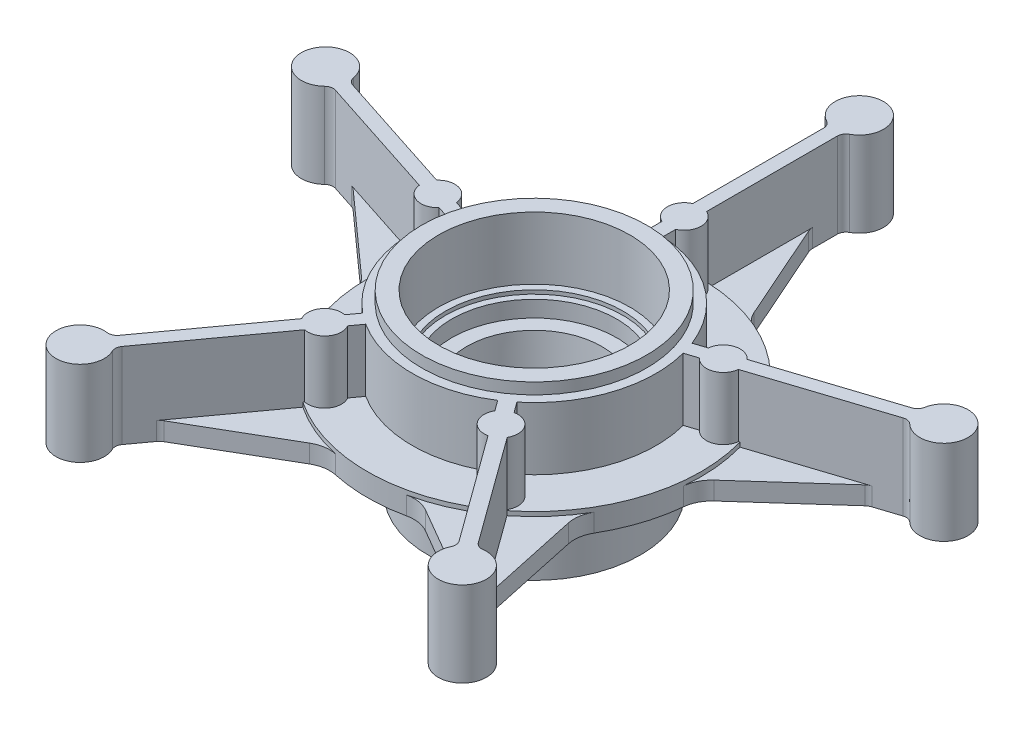
SolidWorks part; units mm, degrees
material "1060 Alloy"
ref_plane "Front Plane" through (0, 0, 0) normal (0, 0, 1) x (1, 0, 0)
ref_plane "Top Plane" through (0, 0, 0) normal (0, 1, 0) x (1, 0, 0)
ref_plane "Right Plane" through (0, 0, 0) normal (1, 0, 0) x (0, 0, -1)
sketch "Sketch1" plane through (0, 0, 0) normal (0, 0, 1) x (1, 0, 0)
  line L1 (89.8423, 2.6099) -> (97.5, 61)
  line L2 (97.5, 61) -> (133.5, 61)
  line L3 (133.5, 61) -> (133.5, 82)
  line L4 (133.5, 82) -> (97.5, 82)
  line L5 (97.5, 82) -> (97.5, 147)
  line L8 (0, 165) -> (0, 0)
  line L15 (71, 147) -> (71, 88)
  line L16 (71, 88) -> (66, 88)
  line L17 (66, 88) -> (66, 75)
  line L18 (66, 75) -> (54, 75)
  line L19 (54, 75) -> (51.5053, 40.9816)
  line L26 (48.5, 0) -> (86.8678, 0)
  line L27 (97.5, 147) -> (71, 147)
  line L28 (48.5, 0) -> (50.8833, 40.5398)
  line L29 (50.8833, 40.5398) -> (51.5053, 40.9816)
  arc A0 (86.8678, 0) -> (89.8423, 2.6099) centre (86.8678, 3) ccw
  point P19 (86, 0)
  point P22 (-86, 0)
  dimension "D10" = 3
  dimension "D2" = 48.5
  dimension "D3" = 133.5
  dimension "D4" = 71
  dimension "D5" = 36
  dimension "D6" = 21
  dimension "D7" = 54
  dimension "D13" = 5
  dimension "D14" = 13
revolve "Revolve1" add sketch "Sketch1" angle 360 about L8
sketch "Sketch2" plane through (0, 82, 0) normal (0, 1, 0) x (1, 0, 0)
  line L0 (-40.8786, 135.0059) -> (-6.3545, 213.0679)
  line L1 (5.5, 236.8593) -> (5.5, 217.1126)
  line L2 (-5.5, 236.8593) -> (-5.5, 217.1126)
  line L3 (0, 260) -> (0, 296.018)
  line L7 (40.8786, 135.0059) -> (6.3545, 213.0679)
  arc A0 (9.1731, 243.0182) -> (-9.1731, 243.0182) centre (0, 260) ccw
  circle A3 centre (0, 0) radius 133.5 construction
  arc A4 (53.6884, 122.2285) -> (-53.6884, 122.2285) centre (0, 0) ccw
  arc A5 (-40.8786, 135.0059) -> (-53.6884, 122.2285) centre (-63.7424, 145.1178) cw
  arc A6 (53.6884, 122.2285) -> (40.8786, 135.0059) centre (63.7424, 145.1178) cw
  arc A7 (6.3545, 213.0679) -> (5.5, 217.1126) centre (15.5, 217.1126) cw
  arc A8 (-6.3545, 213.0679) -> (-5.5, 217.1126) centre (-15.5, 217.1126) ccw
  arc A9 (5.5, 236.8593) -> (9.1731, 243.0182) centre (12.5, 236.8593) cw
  arc A10 (-5.5, 236.8593) -> (-9.1731, 243.0182) centre (-12.5, 236.8593) ccw
  point P15 (-45, 125.6871)
  point P20 (45, 125.6871)
  point P21 (5.5, 215)
  point P24 (-5.5, 215)
  dimension "D1" = 260
  dimension "D2" = 25
  dimension "D3" = 10
  dimension "D4" = 7
  dimension "D5" = 19.301
extrude "Boss-Extrude1" add sketch "Sketch2" against normal blind 21
pattern_circular "CirPattern1" count 5 every 72 about axis through (0, 0, 0) along (0, 1, 0) of "Boss-Extrude1"
sketch "Sketch3" plane through (0, 82, 0) normal (0, 1, 0) x (1, 0, 0)
  circle A0 centre (0, 0) radius 133.5
  circle A1 centre (0, 0) radius 294.6742
extrude "Cut-Extrude1" cut sketch "Sketch3" against normal blind 3.5
sketch "Sketch4" plane through (0, 78.5, 0) normal (0, 1, 0) x (1, 0, 0)
  line L0 (-5.5, 236.8593) -> (-5.5, 132.3288)
  line L1 (5.5, 236.8593) -> (5.5, 132.3288)
  line L2 (5.5, 107.6712) -> (5.5, 97.3447)
  line L3 (-5.5, 107.6712) -> (-5.5, 97.3447)
  arc A0 (9.1731, 243.0182) -> (-9.1731, 243.0182) centre (0, 260) ccw
  arc A1 (9.1731, 243.0182) -> (5.5, 236.8593) centre (12.5, 236.8593) ccw
  arc A2 (-5.5, 236.8593) -> (-9.1731, 243.0182) centre (-12.5, 236.8593) ccw
  arc A3 (5.5, 97.3447) -> (-5.5, 97.3447) centre (0, 0) ccw
  arc A4 (5.5, 107.6712) -> (5.5, 132.3288) centre (0, 120) ccw
  arc A5 (-5.5, 132.3288) -> (-5.5, 107.6712) centre (0, 120) ccw
  dimension "D1" = 27
  dimension "D2" = 140
extrude "Boss-Extrude2" add sketch "Sketch4" along normal blind 68
pattern_circular "CirPattern2" count 5 every 72 about axis through (0, 0, 0) along (0, 1, 0) of "Boss-Extrude2"
sketch "Sketch6" plane through (0, 147, 0) normal (0, 1, 0) x (1, 0, 0)
  circle A0 centre (0, 0) radius 312.0658
extrude "Cut-Extrude3" cut sketch "Sketch6" against normal blind 15
sketch "Sketch7" plane through (0, 132, 0) normal (0, 1, 0) x (1, 0, 0)
  circle A0 centre (0, 0) radius 90
  circle A1 centre (0, 0) radius 71
  dimension "D1" = 180
extrude "Boss-Extrude3" add sketch "Sketch7" along normal blind 9
sketch "Sketch8" plane through (0, 141, 0) normal (0, 1, 0) x (1, 0, 0)
  circle A0 centre (0, 0) radius 76.5
  dimension "D1" = 153
extrude "Cut-Extrude4" cut sketch "Sketch8" against normal blind 50
sketch "Sketch9" plane through (0, 61, 0) normal (0, -1, 0) x (1, 0, 0)
  circle A0 centre (0, 0) radius 94
  circle A1 centre (0, 0) radius 313.8454
extrude "Cut-Extrude5" cut sketch "Sketch9" against normal blind 3
sketch "Sketch10" plane through (0, 0, 0) normal (0, -1, 0) x (1, 0, 0)
  circle A0 centre (0, 0) radius 85
  circle A1 centre (0, 0) radius 106.7606
  dimension "D1" = 170
extrude "Cut-Extrude6" cut sketch "Sketch10" against normal blind 34
sketch "Sketch11" plane through (0, 34, 0) normal (0, -1, 0) x (1, 0, 0)
  circle A0 centre (0, 0) radius 89.5
  circle A1 centre (0, 0) radius 112.8729
  dimension "D1" = 179
extrude "Cut-Extrude7" cut sketch "Sketch11" against normal blind 30
sketch "Sketch12" plane through (0, 0, 0) normal (0, -1, 0) x (1, 0, 0)
  circle A0 centre (0, 0) radius 67.5
  circle A1 centre (0, 0) radius 45
  dimension "D1" = 135
extrude "Boss-Extrude4" add sketch "Sketch12" along normal blind 1
sketch "Sketch13" plane through (0, 0, 0) normal (0, 1, 0) x (1, 0, 0)
  circle A0 centre (0, 0) radius 48.5
extrude "Cut-Extrude8" cut sketch "Sketch13" against normal through all both and the other way through all
